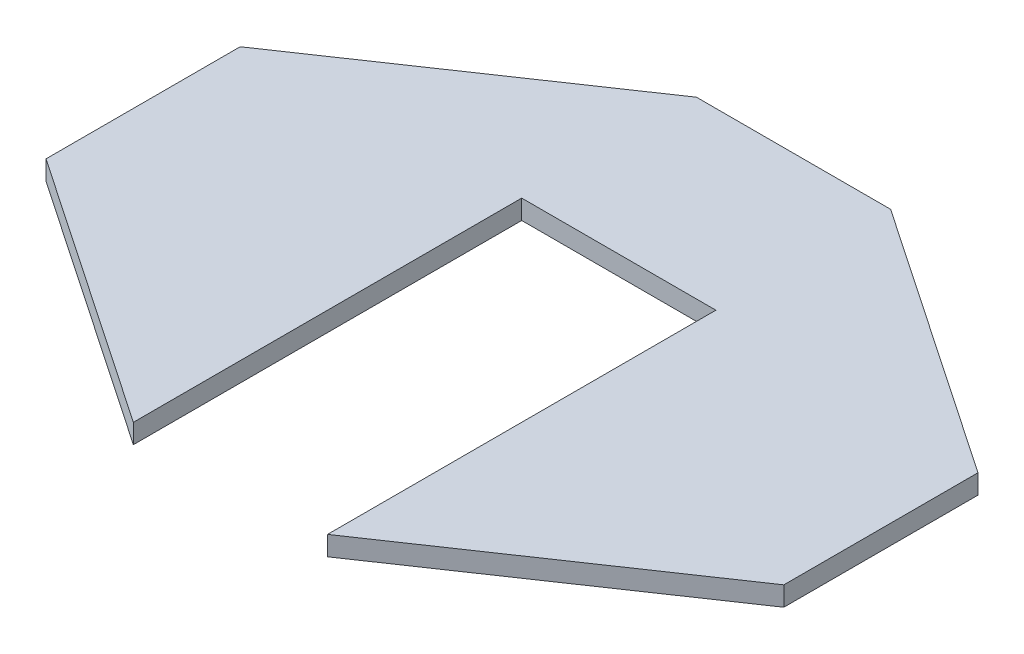
SolidWorks part; units mm, degrees
material "Balsa"
ref_plane "Plan de face" through (0, 0, 0) normal (0, 0, 1) x (1, 0, 0)
ref_plane "Plan de dessus" through (0, 0, 0) normal (0, 1, 0) x (1, 0, 0)
ref_plane "Plan de droite" through (0, 0, 0) normal (1, 0, 0) x (0, 0, -1)
sketch "Esquisse1" plane through (0, 0, 0) normal (0, 1, 0) x (1, 0, 0)
  line L0 (-76.6432, -51.4013) -> (63.3568, 43.5987)
  line L1 (63.3568, 43.5987) -> (163.3568, 43.5987)
  line L2 (-76.6432, -51.4013) -> (-76.6432, -151.4013)
  line L3 (63.3568, -246.4013) -> (163.3568, -246.4013)
  line L4 (303.3568, -51.4013) -> (303.3568, -151.4013)
  line L5 (163.3568, 43.5987) -> (303.3568, -51.4013)
  line L6 (163.3568, -246.4013) -> (303.3568, -151.4013)
  line L7 (-76.6432, -151.4013) -> (63.3568, -246.4013)
  point P0 (-76.6432, 43.5987)
  point P1 (303.3568, -246.4013)
  point P2 (-76.6432, -246.4013)
  point P3 (303.3568, 43.5987)
  dimension "D1" = 380
  dimension "D2" = 290
  dimension "D3" = 140
  dimension "D4" = 95
  dimension "D5" = 140
  dimension "D6" = 95
  dimension "D7" = 140
  dimension "D8" = 95
  dimension "D9" = 95
  dimension "D10" = 140
extrude "Boss.-Extru.1" add sketch "Esquisse1" along normal blind 10 contours L0 L1 L5 L4 L6 L3 L7 L2
sketch "Esquisse3" plane through (0, 0, 246.4013) normal (0, 0, 1) x (1, 0, 0)
  line L1 (63.3568, 10) -> (163.3568, 10)
  line L2 (63.3568, 10) -> (63.3568, 0)
  line L3 (63.3568, 0) -> (163.3568, 0)
  line L4 (163.3568, 10) -> (163.3568, 0)
extrude "Enlèv. mat.-Extru.1" cut sketch "Esquisse3" against normal blind 200
